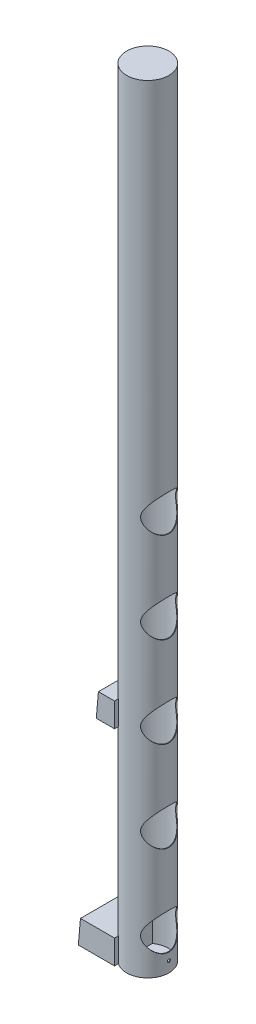
SolidWorks part; units mm, degrees
ref_plane "Спереди" through (0, 0, 0) normal (0, 0, 1) x (1, 0, 0)
ref_plane "Сверху" through (0, 0, 0) normal (0, 1, 0) x (1, 0, 0)
ref_plane "Справа" through (0, 0, 0) normal (1, 0, 0) x (0, 0, -1)
sketch "Эскиз2" plane through (0, 0, 0) normal (0, 1, 0) x (1, 0, 0)
  circle A0 centre (0, 0) radius 35
  circle A1 centre (0, 0) radius 34
  dimension "D1" = 70
  dimension "D2" = 68
extrude "Бобышка-Вытянуть1" add sketch "Эскиз2" along normal blind 1285
sketch "Эскиз3" plane through (0, 0, 0) normal (0, -1, 0) x (1, 0, 0)
  circle A0 centre (0, 0) radius 35
extrude "Бобышка-Вытянуть2" add sketch "Эскиз3" along normal blind 1
sketch "Эскиз4" plane through (0, 1285, 0) normal (0, 1, 0) x (1, 0, 0)
  circle A0 centre (0, 0) radius 35
extrude "Бобышка-Вытянуть3" add sketch "Эскиз4" along normal blind 1
sketch "Эскиз5" plane through (0, 0, 0) normal (1, 0, 0) x (0, 0, -1)
  line L0 (-35, -1) -> (35, -1) construction
  circle A0 centre (0, 16.5) radius 2.5
  circle A1 centre (0, 59) radius 30
  circle A2 centre (0, 209) radius 30
  circle A3 centre (0, 359) radius 30
  circle A4 centre (0, 509) radius 30
  circle A5 centre (0, 659) radius 30
  dimension "D1" = 5
  dimension "D2" = 15
  dimension "D3" = 60
  dimension "D4" = 60
  dimension "D6" = 150
  dimension "D5" = 5
extrude "Вырез-Вытянуть1" cut sketch "Эскиз5" along normal through all
sketch "Эскиз6" plane through (0, 0, 0) normal (1, 0, 0) x (0, 0, -1)
  line L0 (35, 1286) -> (-35, 1286) construction
  circle A0 centre (0, 1271) radius 10
  dimension "D1" = 20
  dimension "D2" = 15
extrude "Вырез-Вытянуть2" cut sketch "Эскиз6" against normal through all
sketch "Эскиз7" plane through (0, 0, 0) normal (1, 0, 0) x (0, 0, -1)
  line L0 (-35, -1) -> (35, -1) construction
  line L1 (-35, 39) -> (35, 39)
  line L2 (-35, 39) -> (-35, -1)
  line L3 (-35, -1) -> (35, -1)
  line L4 (35, 39) -> (35, -1)
  line L5 (-35, 1286) -> (-35, -1) construction
  line L10 (35, -1) -> (35, 1286) construction
  dimension "D1" = 0
  dimension "D2" = 0
  dimension "D3" = 40
extrude "Бобышка-Вытянуть4" add sketch "Эскиз7" against normal blind 60 from offset 20 offset against normal yes
sketch "Эскиз8" plane through (0, 0, 0) normal (1, 0, 0) x (0, 0, -1)
  line L0 (35, -1) -> (35, 1286) construction
  line L1 (-35, 379) -> (35, 379)
  line L2 (-35, 379) -> (-35, 339)
  line L3 (-35, 339) -> (35, 339)
  line L4 (35, 379) -> (35, 339)
  line L5 (-35, 1286) -> (-35, -1) construction
  line L6 (-35, -1) -> (35, -1) construction
  dimension "D1" = 40
  dimension "D2" = 0
  dimension "D3" = 0
  dimension "D4" = 340
extrude "Бобышка-Вытянуть5" add sketch "Эскиз8" along normal blind 30 from offset 50 offset against normal yes
sketch "Эскиз9" plane through (0, 0, 0) normal (0, 0, 1) x (1, 0, 0)
  line L0 (-80, -1) -> (-76.5005, 39)
  line L3 (-50.2539, 339) -> (-46.7543, 379)
  line L6 (-80, 39) -> (-20, 39) construction
  line L7 (-80, -1) -> (-80, 39)
  line L8 (-80, 39) -> (-76.5005, 39)
  line L9 (-20, 379) -> (-50, 379) construction
  line L10 (-46.7543, 379) -> (-50, 379)
  line L11 (-50, 379) -> (-50.2539, 339)
  line L12 (-20, 339) -> (-50, 339) construction
  dimension "D1" = 5
extrude "Вырез-Вытянуть3" cut sketch "Эскиз9" against normal through all both and the other way through all
